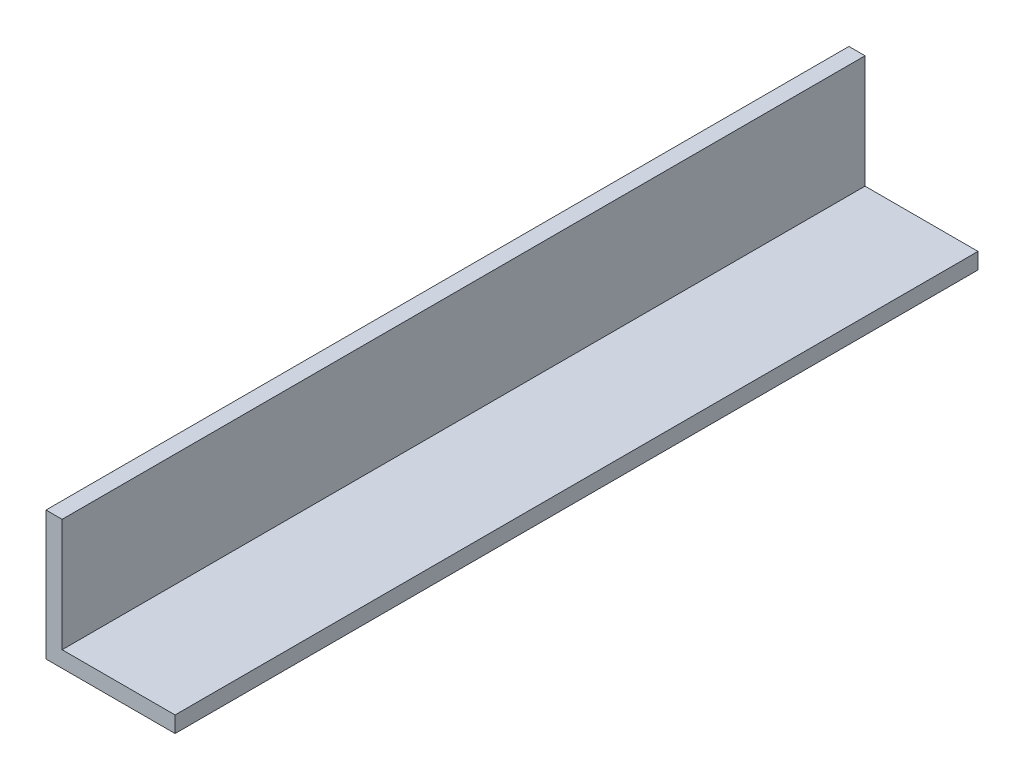
SolidWorks part; units mm, degrees
material "6063-T6"
ref_plane "Front" through (0, 0, 0) normal (0, 0, 1) x (1, 0, 0)
ref_plane "Top" through (0, 0, 0) normal (0, 1, 0) x (1, 0, 0)
ref_plane "Right" through (0, 0, 0) normal (1, 0, 0) x (0, 0, -1)
ref_axis "side-side" through (80.9, 0, 0) along (-1, 0, 0)
ref_axis "up-down" through (0, 50, 0) along (0, -1, 0)
ref_axis "front-back" through (0, 0, -80.9) along (0, 0, 1)
sketch "Sketch1" plane through (0, 0, 0) normal (0, 0, 1) x (1, 0, 0)
  line L1 (0, 0) -> (25.4, 0)
  line L2 (0, 0) -> (0, 25.4)
  line L3 (0, 25.4) -> (3.175, 25.4)
  line L4 (25.4, 0) -> (25.4, 3.175)
  line L7 (25.4, 3.175) -> (3.175, 3.175)
  line L8 (3.175, 25.4) -> (3.175, 3.175)
  dimension "D1" = 3.175
  dimension "D2" = 3.175
  dimension "D3" = 25.4
extrude "Boss-Extrude1" add sketch "Sketch1" along normal blind 158
